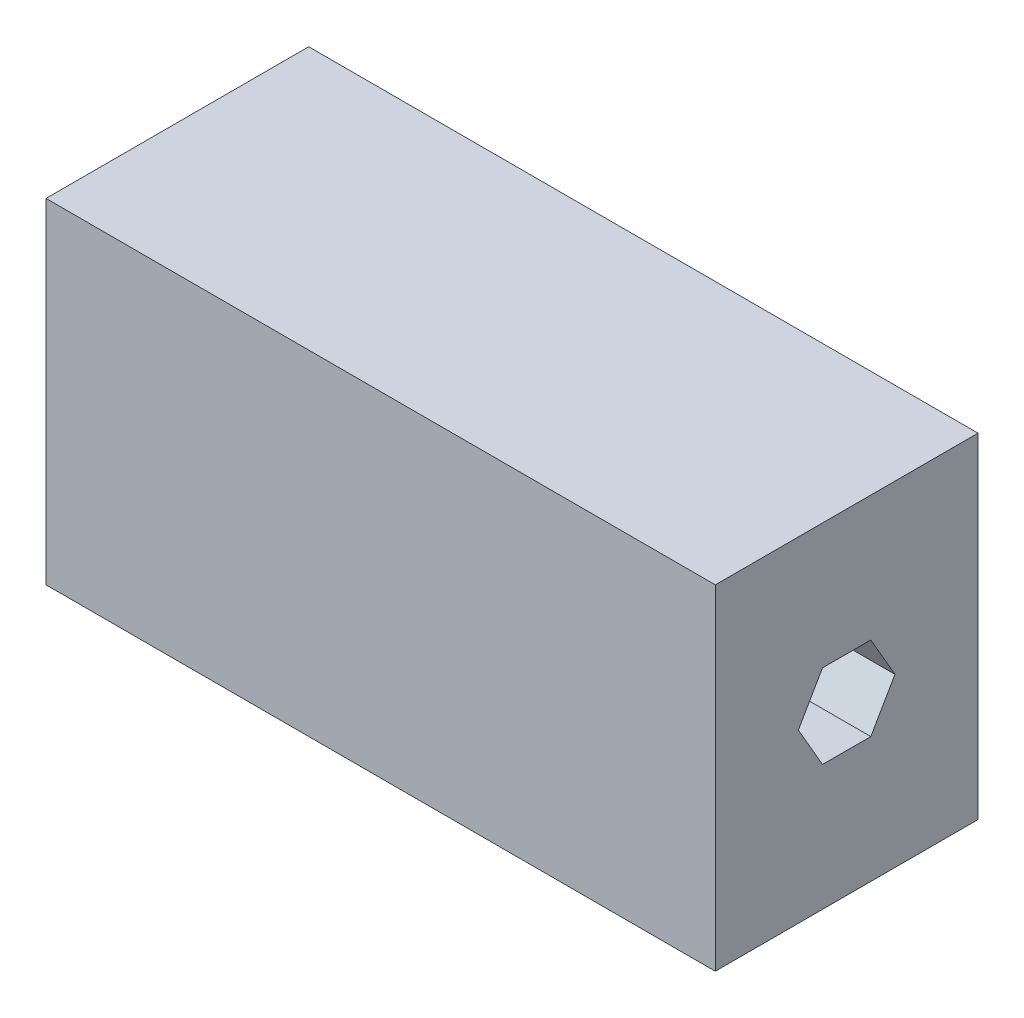
SolidWorks part; units mm, degrees
material "6061-T6 (SS)"
ref_plane "Front" through (0, 0, 0) normal (0, 0, 1) x (1, 0, 0)
ref_plane "Top" through (0, 0, 0) normal (0, 1, 0) x (1, 0, 0)
ref_plane "Right" through (0, 0, 0) normal (1, 0, 0) x (0, 0, -1)
sketch "Sketch1" plane through (0, 0, 0) normal (1, 0, 0) x (0, 0, -1)
  line L1 (19.939, -25.4) -> (-19.939, -25.4)
  line L2 (19.939, -25.4) -> (19.939, 25.4)
  line L3 (19.939, 25.4) -> (-19.939, 25.4)
  line L4 (-19.939, -25.4) -> (-19.939, 25.4)
  line L5 (19.939, -25.4) -> (-19.939, 25.4) construction
  line L6 (19.939, 25.4) -> (-19.939, -25.4) construction
  point P0 (0, 0)
  dimension "D1" = 50.8
  dimension "D2" = 39.878
extrude "Boss-Extrude1" add sketch "Sketch1" along normal blind 101.6
sketch "Sketch3" plane through (101.6, 0, 0) normal (1, 0, 0) x (0, 0, -1)
  line L1 (7.3323, 0) -> (3.6662, 6.35)
  line L2 (3.6662, 6.35) -> (-3.6662, 6.35)
  line L3 (-3.6662, 6.35) -> (-7.3323, 0)
  line L4 (-7.3323, 0) -> (-3.6662, -6.35)
  line L5 (-3.6662, -6.35) -> (3.6662, -6.35)
  line L6 (3.6662, -6.35) -> (7.3323, 0)
  circle A0 centre (0, 0) radius 6.35 construction
  dimension "D1" = 12.7
extrude "Cut-Extrude2" cut sketch "Sketch3" against normal through all
ref_axis "Axis1" through (-80.9, 0, 0) along (1, 0, 0)
